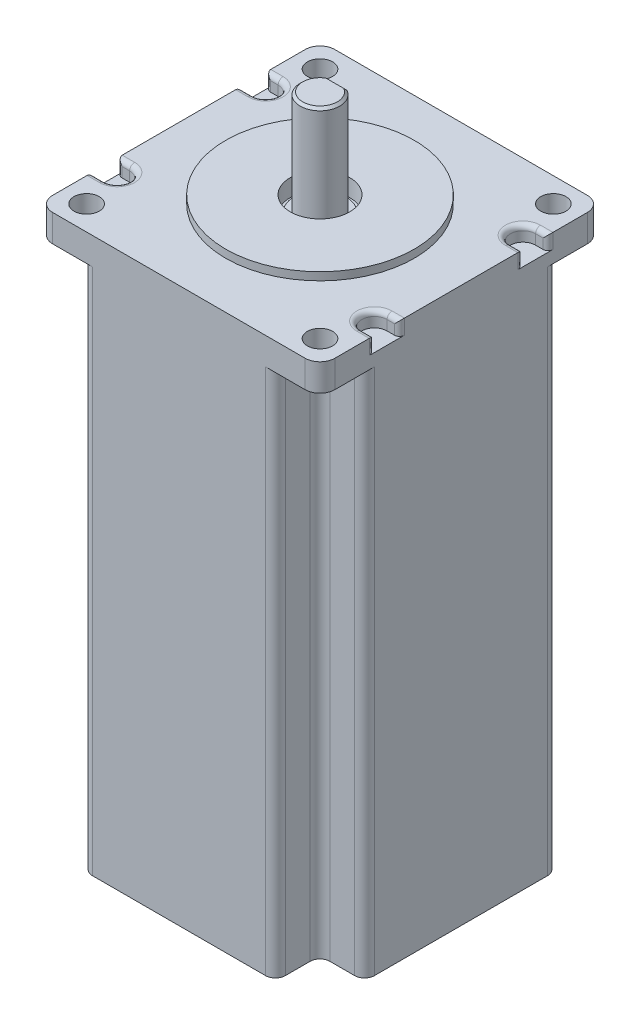
SolidWorks part; units mm, degrees
ref_plane "Front Plane" through (0, 0, 0) normal (0, 0, 1) x (1, 0, 0)
ref_plane "Top Plane" through (0, 0, 0) normal (0, 1, 0) x (1, 0, 0)
ref_plane "Right Plane" through (0, 0, 0) normal (1, 0, 0) x (0, 0, -1)
sketch "Sketch1" plane through (0, 0, 0) normal (0, 1, 0) x (1, 0, 0)
  line L1 (-28.5, 28.5) -> (28.5, 28.5)
  line L2 (-28.5, 28.5) -> (-28.5, -28.5)
  line L3 (-28.5, -28.5) -> (28.5, -28.5)
  line L4 (28.5, 28.5) -> (28.5, -28.5)
  line L5 (-28.5, 28.5) -> (28.5, -28.5) construction
  line L6 (-28.5, -28.5) -> (28.5, 28.5) construction
  point P0 (0, 0)
  dimension "D1" = 57
  dimension "D2" = 57
extrude "Motor rectangular frame" add sketch "Sketch1" along normal blind 112
sketch "Sketch2" plane through (0, 0, 0) normal (0, -1, 0) x (1, 0, 0)
  line L1 (-28.5, 28.5) -> (28.5, 28.5) construction
  line L3 (-28.5, -28.5) -> (-28.5, 28.5) construction
  line L4 (-26.5, 19.5) -> (-21.5, 19.5)
  line L5 (-19.5, 21.5) -> (-19.5, 26.5)
  line L6 (19.5, 26.5) -> (19.5, 21.5)
  line L7 (21.5, 19.5) -> (26.5, 19.5)
  line L8 (28.5, 28.5) -> (28.5, -28.5) construction
  line L10 (26.5, -19.5) -> (21.5, -19.5)
  line L11 (19.5, -21.5) -> (19.5, -26.5)
  line L12 (28.5, -28.5) -> (-28.5, -28.5) construction
  line L14 (-19.5, -26.5) -> (-19.5, -21.5)
  line L15 (-21.5, -19.5) -> (-26.5, -19.5)
  line L16 (-28.5, 17.5) -> (-28.5, 28.5)
  line L17 (-28.5, 28.5) -> (-17.5, 28.5)
  line L18 (-28.5, -17.5) -> (-28.5, -28.5)
  line L19 (-28.5, -28.5) -> (-17.5, -28.5)
  line L20 (17.5, -28.5) -> (28.5, -28.5)
  line L21 (28.5, -28.5) -> (28.5, -17.5)
  line L22 (28.5, 17.5) -> (28.5, 28.5)
  line L23 (28.5, 28.5) -> (17.5, 28.5)
  arc A0 (17.5, 28.5) -> (19.5, 26.5) centre (17.5, 26.5) cw
  arc A1 (19.5, 21.5) -> (21.5, 19.5) centre (21.5, 21.5) ccw
  arc A2 (26.5, 19.5) -> (28.5, 17.5) centre (26.5, 17.5) cw
  arc A3 (28.5, -17.5) -> (26.5, -19.5) centre (26.5, -17.5) cw
  arc A4 (21.5, -19.5) -> (19.5, -21.5) centre (21.5, -21.5) ccw
  arc A5 (19.5, -26.5) -> (17.5, -28.5) centre (17.5, -26.5) cw
  arc A6 (-17.5, -28.5) -> (-19.5, -26.5) centre (-17.5, -26.5) cw
  arc A7 (-19.5, -21.5) -> (-21.5, -19.5) centre (-21.5, -21.5) ccw
  arc A8 (-28.5, -17.5) -> (-26.5, -19.5) centre (-26.5, -17.5) ccw
  arc A9 (-28.5, 17.5) -> (-26.5, 19.5) centre (-26.5, 17.5) cw
  arc A10 (-17.5, 28.5) -> (-19.5, 26.5) centre (-17.5, 26.5) ccw
  arc A11 (-21.5, 19.5) -> (-19.5, 21.5) centre (-21.5, 21.5) ccw
  point P5 (0, 28.5)
  point P13 (-28.5, 0)
  point P28 (19.5, 28.5)
  point P31 (19.5, 19.5)
  point P34 (28.5, 19.5)
  point P37 (28.5, -19.5)
  point P40 (19.5, -19.5)
  point P43 (19.5, -28.5)
  point P46 (-19.5, -28.5)
  point P49 (-19.5, -19.5)
  point P52 (-28.5, -19.5)
  point P55 (-28.5, 19.5)
  point P58 (-19.5, 28.5)
  dimension "D11" = 2
  dimension "D2" = 9
  dimension "D3" = 28.5
  dimension "D4" = 28.5
extrude "Motor screw hole lengths" cut sketch "Sketch2" against normal offset from surface (106.5 mm away) 5.5 up to face at (0, 112, 0)
sketch "Sketch3" plane through (0, 106.5, 0) normal (0, -1, 0) x (1, 0, 0)
  line L0 (0, 0) -> (28.5, 0) construction
  line L1 (28.5, 17.5) -> (28.5, -17.5) construction
  circle A0 centre (-23.57, 23.57) radius 2.55
  circle A1 centre (23.57, 23.57) radius 2.55
  circle A2 centre (23.57, -23.57) radius 2.55
  circle A3 centre (-23.57, -23.57) radius 2.55
  dimension "D3" = 5.1
  dimension "D4" = 5.1
  dimension "D1" = 47.14
  dimension "D2" = 23.57
  dimension "D5" = 23.57
  dimension "D6" = 23.57
extrude "Motor mount holes" cut sketch "Sketch3" against normal through all
sketch "Sketch4" plane through (0, 0, 0) normal (0, -1, 0) x (1, 0, 0)
  circle A0 centre (0, 0) radius 6
  dimension "D1" = 12
extrude "Rear bearing and shaft" cut sketch "Sketch4" against normal blind 4.5
sketch "Sketch5" plane through (0, 4.5, 0) normal (0, -1, 0) x (1, 0, 0)
  circle A0 centre (0, 0) radius 4.5
  circle A1 centre (0, 0) radius 6
  dimension "D1" = 12
  dimension "D2" = 9
extrude "Rear bearing shield" cut sketch "Sketch5" against normal blind 0.5
sketch "Sketch6" plane through (0, 4.5, 0) normal (0, -1, 0) x (1, 0, 0)
  circle A0 centre (0, 0) radius 8
  dimension "D1" = 16
extrude "Hollowed section (rear)" cut sketch "Sketch6" along normal blind 3
sketch "Sketch7" plane through (0, 112, 0) normal (0, 1, 0) x (1, 0, 0)
  circle A0 centre (0, 0) radius 19.05
  dimension "D1" = 38.1
extrude "Front platform extrude" add sketch "Sketch7" along normal blind 1.6
sketch "Sketch8" plane through (0, 113.6, 0) normal (0, 1, 0) x (1, 0, 0)
  circle A0 centre (0, 0) radius 6
  dimension "D1" = 12
extrude "Front bearing" cut sketch "Sketch8" against normal blind 3
sketch "Sketch9" plane through (0, 110.6, 0) normal (0, 1, 0) x (1, 0, 0)
  line L0 (0, -4) -> (0, 3.5) construction
  line L1 (-1.9365, 3.5) -> (1.9365, 3.5)
  arc A0 (-1.9365, 3.5) -> (1.9365, 3.5) centre (0, 0) ccw
  point P9 (0, 3.5)
  dimension "D1" = 8
  dimension "D2" = 7.5
extrude "Front shaft" add sketch "Sketch9" along normal blind 21
sketch "Sketch10" plane through (0, 110.6, 0) normal (0, 1, 0) x (1, 0, 0)
  circle A0 centre (0, 0) radius 5.25
  circle A1 centre (0, 0) radius 6
  dimension "D1" = 10.5
  dimension "D2" = 12
extrude "Front bearing sheild" cut sketch "Sketch10" against normal blind 0.5
chamfer "Motor shaft chamfer" distance 0.5 angle 45 2 edges at (0, 131.6, -3.5) (0, 131.6, 4)
fillet "Motor front edge fillet" radius 3 4 edges at (-28.5, 109.25, -28.5) (28.5, 109.25, -28.5) (-28.5, 109.25, 28.5) (28.5, 109.25, 28.5)
sketch "Sketch11" plane through (0, 112, 0) normal (0, 1, 0) x (1, 0, 0)
  line L0 (26, 17.55) -> (28.5, 17.55)
  line L1 (28.5, -25.5) -> (28.5, 25.5) construction
  line L2 (26, 12.45) -> (28.5, 12.45)
  line L3 (26, -12.45) -> (28.5, -12.45)
  line L4 (26, -17.55) -> (28.5, -17.55)
  line L5 (28.5, -12.45) -> (28.5, -17.55)
  line L6 (28.5, 17.55) -> (28.5, 12.45)
  line L7 (0, 0) -> (0, 28.5) construction
  line L8 (25.5, 28.5) -> (-25.5, 28.5) construction
  line L9 (-26, -12.45) -> (-28.5, -12.45)
  line L10 (-28.5, -12.45) -> (-28.5, -17.55)
  line L11 (-26, -17.55) -> (-28.5, -17.55)
  line L12 (-26, 17.55) -> (-28.5, 17.55)
  line L13 (-26, 12.45) -> (-28.5, 12.45)
  line L14 (-28.5, 17.55) -> (-28.5, 12.45)
  arc A0 (26, 17.55) -> (26, 12.45) centre (26, 15) ccw
  arc A1 (26, -12.45) -> (26, -17.55) centre (26, -15) ccw
  arc A2 (-26, -12.45) -> (-26, -17.55) centre (-26, -15) cw
  arc A3 (-26, 17.55) -> (-26, 12.45) centre (-26, 15) cw
  dimension "D3" = 5.1
  dimension "D4" = 5.1
  dimension "D1" = 15
  dimension "D2" = 15
  dimension "D5" = 26
  dimension "D6" = 26
extrude "Front cover screw indents" cut sketch "Sketch11" against normal blind 3
fillet "Front cover screw indent fillet" radius 1 20 edges at (27.25, 112, 12.45) (27.25, 112, 17.55) (27.25, 112, -17.55) (27.25, 112, -12.45) (-27.25, 112, -12.45) (-27.25, 112, -17.55) (-27.25, 112, 17.55) (-27.25, 112, 12.45) (23.45, 112, 15) (23.45, 112, -15) (-23.45, 112, -15) (-23.45, 112, 15) (-28.5, 110.5, 17.55) (-28.5, 110.5, 12.45) (-28.5, 110.5, -12.45) (-28.5, 110.5, -17.55) (28.5, 110.5, -17.55) (28.5, 110.5, -12.45) (28.5, 110.5, 12.45) (28.5, 110.5, 17.55)
sketch "Sketch12" plane through (0, 0, -28.5) normal (0, 0, -1) x (-1, 0, 0)
  line L0 (-3.5, 0) -> (3.5, 0)
  line L1 (-17.5, 0) -> (17.5, 0) construction
  line L2 (-3.5, 0) -> (-3.5, 5)
  line L3 (-3.5, 5) -> (3.5, 5)
  line L4 (3.5, 5) -> (3.5, 0)
  line L5 (-3.5, 0) -> (3.5, 5) construction
  line L7 (-2.5, 4.5) -> (2.5, 4.5)
  line L8 (-2.5, 4.5) -> (-2.5, 0.5)
  line L9 (-2.5, 0.5) -> (2.5, 0.5)
  line L10 (2.5, 4.5) -> (2.5, 0.5)
  line L11 (-2.5, 4.5) -> (2.5, 0.5) construction
  line L12 (-2.5, 0.5) -> (2.5, 4.5) construction
  point P0 (0, 2.5)
  point P5 (0, 0)
  dimension "D1" = 7
  dimension "D2" = 5
  dimension "D3" = 5
  dimension "D4" = 4
extrude "Wire area" add sketch "Sketch12" along normal blind 3
